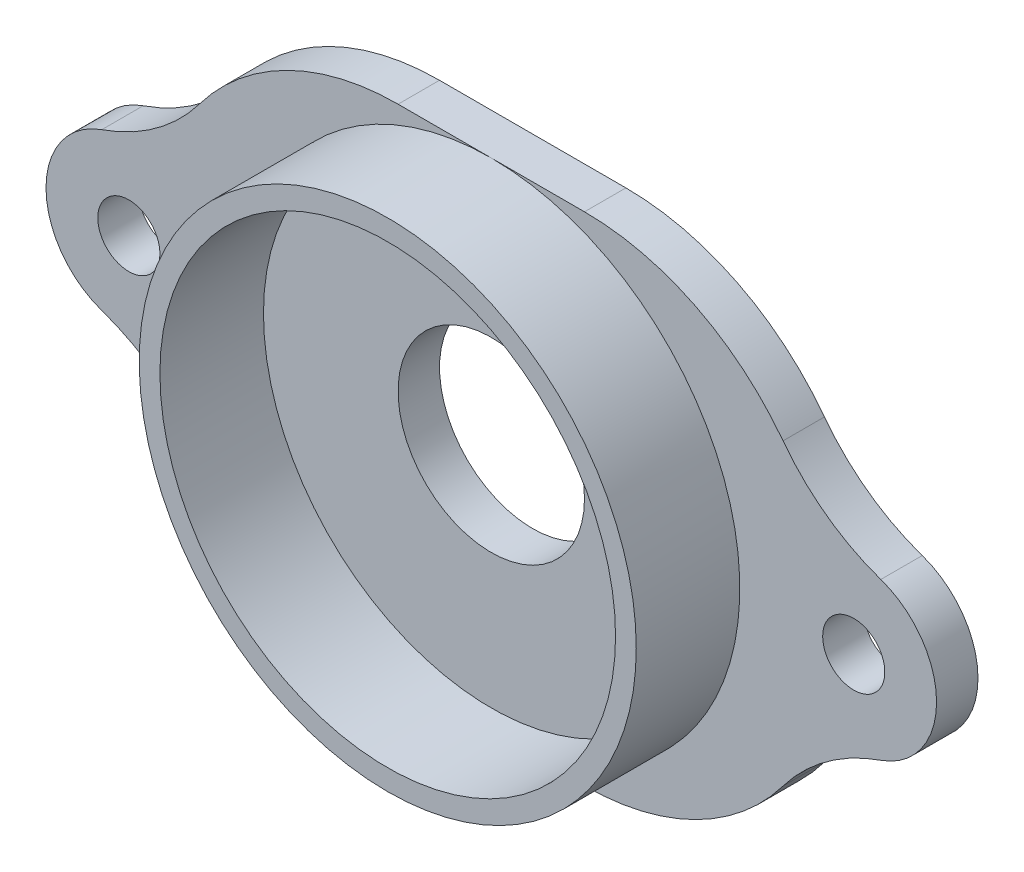
SolidWorks part; units mm, degrees
ref_plane "前视基准面" through (0, 0, 0) normal (0, 0, 1) x (1, 0, 0)
ref_plane "上视基准面" through (0, 0, 0) normal (0, 1, 0) x (1, 0, 0)
ref_plane "右视基准面" through (0, 0, 0) normal (1, 0, 0) x (0, 0, -1)
sketch "草图2" plane through (0, 0, 0) normal (0, 0, 1) x (1, 0, 0)
  line L0 (0, 0) -> (23.5174, 0) construction
  line L1 (0, 0) -> (0, 15) construction
  line L8 (-4.5, 12) -> (4.5, 12)
  line L9 (-4.5, -12) -> (4.5, -12)
  arc A0 (4.5, 12) -> (14.0874, 7.2168) centre (4.5, 0) cw
  arc A1 (18.8077, -3.7802) -> (18.8077, 3.7802) centre (17.5, 0) ccw
  arc A2 (14.0874, 7.2168) -> (18.8077, 3.7802) centre (22.0769, 13.2307) ccw
  arc A3 (-14.0874, 7.2168) -> (-18.8077, 3.7802) centre (-22.0769, 13.2307) cw
  arc A4 (-4.5, 12) -> (-14.0874, 7.2168) centre (-4.5, 0) ccw
  arc A5 (14.0874, -7.2168) -> (18.8077, -3.7802) centre (22.0769, -13.2307) cw
  arc A6 (4.5, -12) -> (14.0874, -7.2168) centre (4.5, 0) ccw
  arc A7 (-4.5, -12) -> (-14.0874, -7.2168) centre (-4.5, 0) cw
  arc A8 (-14.0874, -7.2168) -> (-18.8077, -3.7802) centre (-22.0769, -13.2307) ccw
  arc A9 (-18.8077, -3.7802) -> (-18.8077, 3.7802) centre (-17.5, 0) cw
  point P10 (0, 0)
  point P13 (0, 0)
  point P22 (0, 7.5)
  dimension "D2" = 8
  dimension "D6" = 12
  dimension "D7" = 10
  dimension "D4" = 17.5
extrude "凸台-拉伸2" add sketch "草图2" along normal mid plane 2 contours A4 A3 A9 A8 A7 L9 A6 A5 A1 A2 A0 L8
sketch "草图3" plane through (0, 0, 1) normal (0, 0, 1) x (1, 0, 0)
  line L0 (-4.5, -12) -> (4.5, -12) construction
  circle A0 centre (0, 0) radius 11
  circle A1 centre (0, 0) radius 12
  dimension "D1" = 22
extrude "凸台-拉伸3" add sketch "草图3" along normal blind 5
sketch "草图4" plane through (0, 0, 1) normal (0, 0, 1) x (1, 0, 0)
  circle A0 centre (0, 0) radius 4.5
  dimension "D1" = 9
extrude "切除-拉伸1" cut sketch "草图4" against normal through all
sketch "草图5" plane through (0, 0, -1) normal (0, 0, -1) x (-1, 0, 0)
  circle A0 centre (17.5, 0) radius 1.5
  circle A1 centre (-17.5, 0) radius 1.5
  dimension "D1" = 3
  dimension "D2" = 3
extrude "切除-拉伸2" cut sketch "草图5" against normal through all
